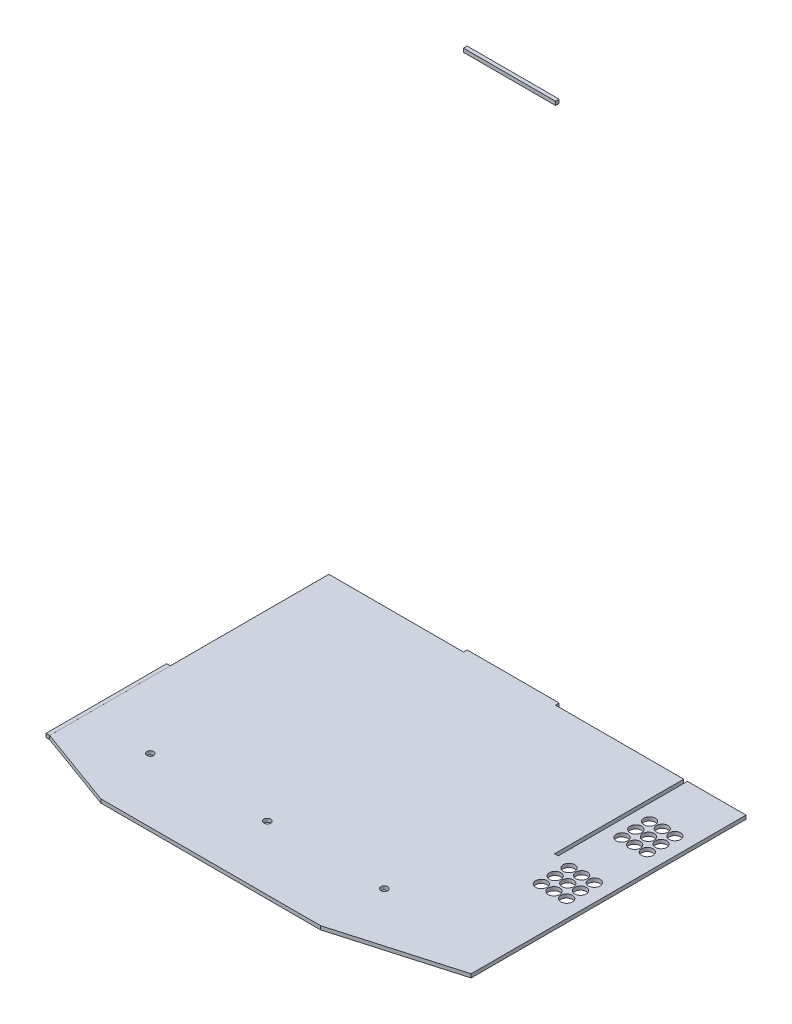
SolidWorks part; units mm, degrees
material "6061-T6 (SS)"
ref_plane "X-Y Datum" through (0, 0, 0) normal (0, 0, 1) x (1, 0, 0)
ref_plane "X-Z Datum" through (0, 0, 0) normal (0, 1, 0) x (1, 0, 0)
ref_plane "Y-Z Datum" through (0, 0, 0) normal (1, 0, 0) x (0, 0, -1)
sketch "Sketch1" plane through (0, 0, 0) normal (0, 0, 1) x (1, 0, 0)
  line L1 (-154.0556, -1.5875) -> (154.0556, -1.5875)
  line L2 (-154.0556, -1.5875) -> (-154.0556, 1.5875)
  line L3 (-154.0556, 1.5875) -> (154.0556, 1.5875)
  line L4 (154.0556, -1.5875) -> (154.0556, 1.5875)
  line L5 (-154.0556, -1.5875) -> (154.0556, 1.5875) construction
  line L6 (-154.0556, 1.5875) -> (154.0556, -1.5875) construction
  point P0 (0, 0)
  dimension "D1" = 3.175
  dimension "D2" = 308.1112
extrude "Boss-Extrude1" add sketch "Sketch1" along normal blind 267.83
sketch "Sketch3" plane through (154.0556, 0, 0) normal (1, 0, 0) x (0, 0, -1)
  line L0 (-267.83, 1.5875) -> (0, 1.5875) construction
  line L1 (-267.83, -1.5875) -> (-112.128, -1.5875)
  line L2 (-267.83, -1.5875) -> (-267.83, 1.5875)
  line L3 (-267.83, 1.5875) -> (-112.128, 1.5875)
  line L4 (-112.128, -1.5875) -> (-112.128, 1.5875)
  dimension "D1" = 155.702
extrude "Boss-Extrude3" add sketch "Sketch3" along normal blind 3.175
sketch "Sketch4" plane through (0, 0, 267.83) normal (0, 0, 1) x (1, 0, 0)
  line L1 (157.2306, -1.5875) -> (208.1043, -1.5875)
  line L2 (157.2306, -1.5875) -> (157.2306, 1.5875)
  line L3 (157.2306, 1.5875) -> (208.1043, 1.5875)
  line L4 (208.1043, -1.5875) -> (208.1043, 1.5875)
  dimension "D1" = 3.175
  dimension "D2" = 50.8737
extrude "Boss-Extrude4" add sketch "Sketch4" against normal blind 267.83
sketch "Sketch6" plane through (0, 1.5875, 0) normal (0, 1, 0) x (1, 0, 0)
  line L0 (106.5043, -267.83) -> (106.5043, -223.38)
  line L1 (208.1043, -267.83) -> (-154.0556, -267.83) construction
  line L2 (208.1043, -223.38) -> (106.5043, -223.38)
  line L3 (208.1043, 0) -> (208.1043, -267.83) construction
  line L5 (106.5043, -267.83) -> (208.1047, -238.62)
  line L6 (208.1043, -223.38) -> (208.1047, -238.62)
  line M9 (-154.0556, -267.83) -> (208.1043, -267.83)
  line M10 (208.1043, -267.83) -> (208.1043, 0)
  dimension "D1" = 44.45
  dimension "D2" = 101.6
  dimension "D3" = 15.24
extrude "Cut-Extrude1" cut sketch "Sketch6" against normal through all contours L5 M9 M10 region at (174.2376, 1.5875, 258.0934)
sketch "Sketch11" plane through (0, -1.5875, 0) normal (0, -1, 0) x (1, 0, 0)
  line L0 (-84.2056, 267.83) -> (-84.2056, 242.43)
  line L1 (-154.0556, 267.83) -> (106.5043, 267.83) construction
  line L2 (-154.0556, 242.43) -> (-84.2056, 242.43)
  line L3 (-154.0556, 267.83) -> (-154.0556, 0) construction
  line L4 (-154.0556, 242.43) -> (-84.2056, 267.83)
  line M4 (-154.0556, 267.83) -> (-154.0556, 0)
  line M18 (106.5043, 267.83) -> (-154.0556, 267.83)
  dimension "D1" = 69.85
  dimension "D2" = 25.4
extrude "Cut-Extrude3" cut sketch "Sketch11" against normal through all contours L4 M4 M18 region at (-130.7723, -1.5875, 259.3633)
sketch "Sketch13" plane through (0, -1.5875, 0) normal (0, -1, 0) x (1, 0, 0)
  circle A6 centre (171.0499, 116.6448) radius 5
  circle A7 centre (182.0499, 116.6448) radius 5
  circle A8 centre (193.0499, 116.6448) radius 5
  circle A9 centre (171.0499, 46.6448) radius 5
  circle A10 centre (182.0499, 46.6448) radius 5
  circle A11 centre (193.0499, 46.6448) radius 5
extrude "Cut-Extrude4" cut sketch "Sketch13" against normal through all
pattern_linear "LPattern1" count 3 spacing 12 along (0, 0, 1) of "Cut-Extrude4"
sketch "Sketch17" plane through (-154.0556, 0, 0) normal (-1, 0, 0) x (0, 0, 1)
  line L1 (137.65, -1.577) -> (242.425, -1.577)
  line L2 (137.65, -1.577) -> (137.65, 1.598)
  line L3 (137.65, 1.598) -> (242.425, 1.598)
  line L4 (242.425, -1.577) -> (242.425, 1.598)
extrude "Boss-Extrude5" add sketch "Sketch17" along normal blind 3.175
sketch "Sketch18" plane through (0, 0, 0) normal (0, 0, -1) x (-1, 0, 0)
  line L0 (-154.0556, 1.5875) -> (154.0556, 1.5875) construction
  line L1 (-42.784, 1.5875) -> (37.216, 1.5875)
  line L2 (-42.784, 1.5875) -> (-42.784, -1.5875)
  line L3 (-42.784, -1.5875) -> (37.216, -1.5875)
  line L4 (37.216, 1.5875) -> (37.216, -1.5875)
  line L5 (-42.784, 1.5875) -> (-42.784, -1.5875) construction
  line L6 (154.0556, -1.5875) -> (-154.0556, -1.5875) construction
  line L7 (37.216, 1.5875) -> (37.216, -1.5875) construction
extrude "Boss-Extrude6" add sketch "Sketch18" along normal blind 3.175
sketch "Sketch19" plane through (0, 0, 0) normal (0, 0, -1) x (-1, 0, 0)
  line L1 (37.216, 455.6355) -> (-42.784, 455.6355)
  line L2 (37.216, 455.6355) -> (37.216, 452.4605)
  line L3 (37.216, 452.4605) -> (-42.784, 452.4605)
  line L4 (-42.784, 455.6355) -> (-42.784, 452.4605)
extrude "Boss-Extrude7" add sketch "Sketch19" along normal blind 3.175 separate body
sketch "Sketch20" [suppressed] plane through (0, -1.5875, 0) normal (0, -1, 0) x (1, 0, 0)
  circle A0 centre (182.0334, 231.4731) radius 2 construction
  circle A1 centre (125.8671, 252.5775) radius 2 construction
  circle A2 centre (63.0495, 261.5116) radius 2 construction
  circle A3 centre (12.2495, 261.5116) radius 2 construction
  circle A4 centre (-38.5505, 261.5116) radius 2 construction
  circle A5 centre (-100.9036, 255.0014) radius 2 construction
  circle A6 centre (-133.9829, 242.9725) radius 2 construction
  circle A7 centre (182.0334, 231.4731) radius 2
  circle A8 centre (125.8671, 252.5775) radius 2
  circle A9 centre (63.0495, 261.5116) radius 2
  circle A10 centre (12.2495, 261.5116) radius 2
  circle A11 centre (-38.5505, 261.5116) radius 2
  circle A12 centre (-100.9036, 255.0014) radius 2
  circle A13 centre (-133.9829, 242.9725) radius 2
extrude "Cut-Extrude5" [suppressed] cut sketch "Sketch20" against normal blind 3.175
sketch "Sketch22" plane through (0, 1.5875, 0) normal (0, 1, 0) x (1, 0, 0)
  circle A0 centre (-96.7719, -212.3068) radius 0.0276
  circle A1 centre (-96.7719, -212.3068) radius 3
  dimension "D1" = 6
extrude "Cut-Extrude6" cut sketch "Sketch22" against normal through all
pattern_linear "LPattern2" count 3 spacing 101.6 along (1, 0, 0) of "Cut-Extrude6"
